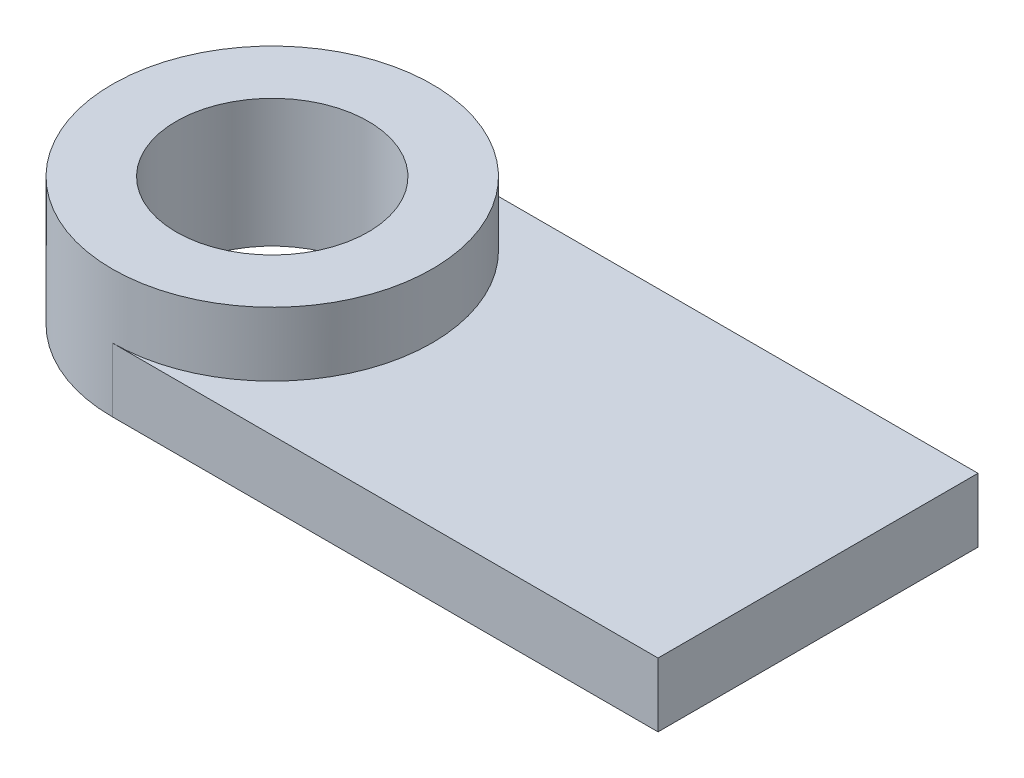
SolidWorks part; units mm, degrees
ref_plane "Front Plane" through (0, 0, 0) normal (0, 0, 1) x (1, 0, 0)
ref_plane "Top Plane" through (0, 0, 0) normal (0, 1, 0) x (1, 0, 0)
ref_plane "Right Plane" through (0, 0, 0) normal (1, 0, 0) x (0, 0, -1)
sketch "Sketch1" plane through (0, 0, 0) normal (0, 1, 0) x (1, 0, 0)
  line L3 (0, -15.875) -> (54.1546, -15.875)
  line L4 (54.1546, -15.875) -> (54.1546, 15.875)
  line L5 (54.1546, 15.875) -> (0, 15.875)
  line L6 (54.1546, -3.302) -> (15.5278, -3.302) construction
  line L7 (54.1546, 0) -> (-15.875, 0) construction
  line L8 (54.1546, 3.302) -> (15.5278, 3.302) construction
  line L9 (0, 0) -> (-11.2253, -11.2253) construction
  circle A3 centre (0, 0) radius 9.525
  circle A4 centre (0, 0) radius 15.875
  arc A5 (0, -15.875) -> (0, 15.875) centre (0, 0) ccw
  dimension "D2" = 19.05
  dimension "D3" = 31.75
  dimension "D1" = 54.1546
  dimension "D4" = 3.302
  dimension "D5" = 45
extrude "Boss-Extrude1" add sketch "Sketch1" along normal blind 12.7 contours A4 A3 region at (-15.426, 0, 0)
extrude "Boss-Extrude2" add sketch "Sketch1<6>" along normal blind 6.35 contours A4 L3 L4 L5 region at (33.1608, 0, 0)
sketch "Sketch1<6>" plane through (0, 0, 0) normal (0, 1, 0) x (1, 0, 0) same geometry as "Sketch1"
